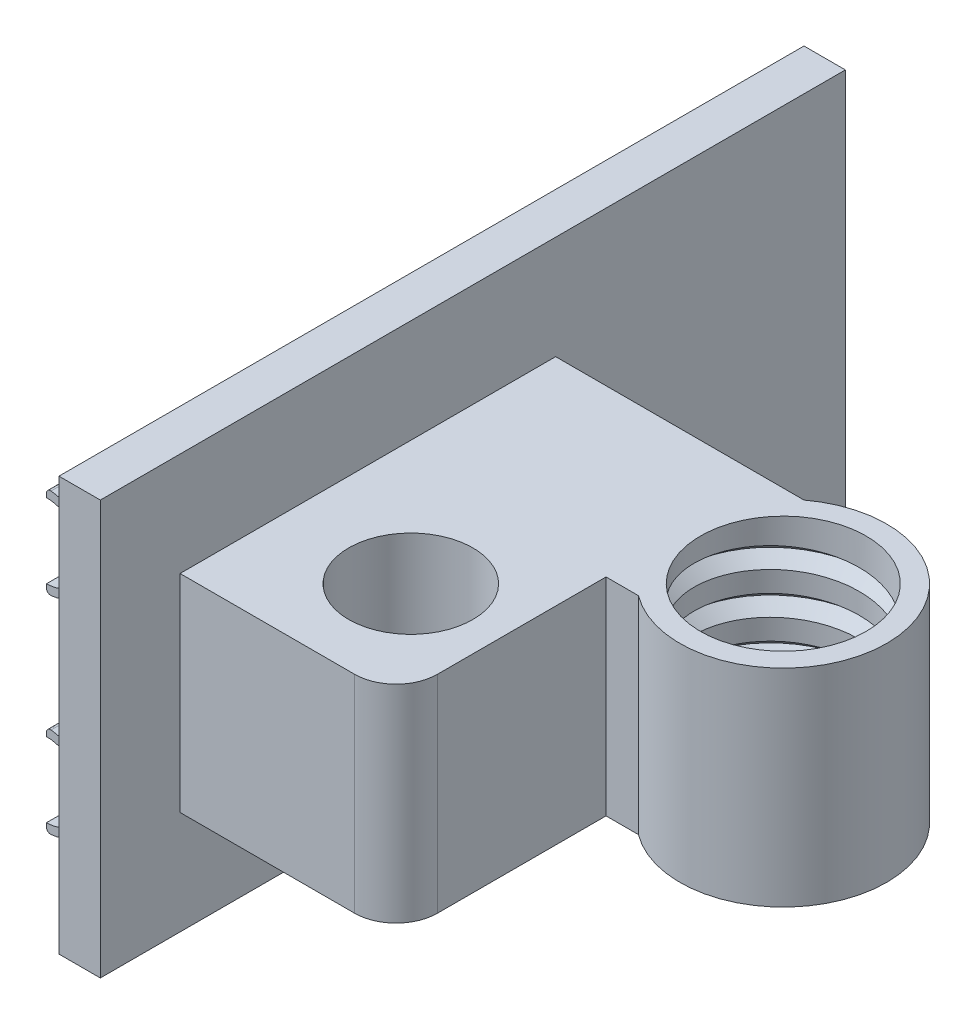
SolidWorks part; units mm, degrees
ref_plane "Front Plane" through (0, 0, 0) normal (0, 0, 1) x (1, 0, 0)
ref_plane "Top Plane" through (0, 0, 0) normal (0, 1, 0) x (1, 0, 0)
ref_plane "Right Plane" through (0, 0, 0) normal (1, 0, 0) x (0, 0, -1)
sketch "Sketch1" plane through (0, 0, 0) normal (0, 1, 0) x (1, 0, 0)
  line L0 (-75, 20) -> (-75, -20)
  line L1 (-15, 20) -> (-75, 20)
  line L3 (-75, -20) -> (-15, -20)
  circle A0 centre (0, 0) radius 20
  arc A1 (-15, -20) -> (-15, 20) centre (0, 0) ccw
  dimension "D1" = 40
  dimension "D2" = 50
  dimension "D3" = 60
extrude "Boss-Extrude1" add sketch "Sketch1" along normal blind 50
sketch "Sketch2" plane through (-75, 0, 0) normal (-1, 0, 0) x (0, 0, 1)
  line L0 (20, 50) -> (-20, 0)
  line L1 (-20, 50) -> (20, 0)
  line L3 (-90, -25) -> (90, -25)
  line L4 (-90, -25) -> (-90, 75)
  line L5 (-90, 75) -> (90, 75)
  line L6 (90, -25) -> (90, 75)
  line L7 (-90, -25) -> (90, 75) construction
  line L8 (-90, 75) -> (90, -25) construction
  point P8 (0, 25)
  dimension "D1" = 180
  dimension "D2" = 100
extrude "Boss-Extrude2" add sketch "Sketch2" along normal blind 10 contours L4 L5 L6 L3
sketch "Sketch11" plane through (0, 0, 0) normal (0, 0, 1) x (1, 0, 0)
  line L0 (-20, 50) -> (20, 50) construction
  line L1 (20, 50) -> (-20, 50) construction
  line L2 (25, 50) -> (-15, 50) construction
  line L3 (0, 50) -> (0, 0) construction
  line L4 (20, 50) -> (20, 45)
  line L5 (20, 45) -> (23.047, 47.5)
  line L6 (23.047, 47.5) -> (20, 50)
  dimension "D1" = 5
sketch "Sketch12" plane through (0, 50, 0) normal (0, 1, 0) x (1, 0, 0)
  circle A0 centre (0, 0) radius 20.1308
ref_plane "Plane2" through (0, 60, 0) normal (0, 1, 0) x (1, 0, 0)
sketch "Sketch13" plane through (0, 60, 0) normal (0, 1, 0) x (1, 0, 0)
  circle A0 centre (0, 0) radius 20 construction
  circle A1 centre (0, 0) radius 20
curve "Helix/Spiral2" pitch 10 height 72.5 turns 7.25
sweep "Cut-Sweep2" cut profiles "Sketch11" path "Helix/Spiral2"
sketch "Sketch14" plane through (0, 0, 90) normal (0, 0, 1) x (1, 0, 0)
  line L0 (-85, 25) -> (-85, 75) construction
  line L1 (-85, 25) -> (-116.7737, 25) construction
  line L2 (-85, 50) -> (-98, 50) construction
  line L3 (-85, 55.4817) -> (-88.4632, 55.4817)
  line L4 (-85, 44.5183) -> (-88.4632, 44.5183)
  line L5 (-98, 39) -> (-98, 41)
  line L6 (-98, 59) -> (-98, 61)
  line L7 (-85, 44.5183) -> (-85, 55.4817)
  line L8 (-85, 0) -> (-98, 0) construction
  line L9 (-85, 5.4817) -> (-85, -5.4817)
  line L10 (-98, -9) -> (-98, -11)
  line L11 (-98, 11) -> (-98, 9)
  line L12 (-85, 5.4817) -> (-88.4632, 5.4817)
  line L13 (-85, -5.4817) -> (-88.4632, -5.4817)
  arc A1 (-98, 39) -> (-88.4632, 44.5183) centre (-98, 50) ccw
  arc A2 (-90.862, 55.4817) -> (-98, 59) centre (-98, 50) ccw
  arc A3 (-90.862, 44.5183) -> (-98, 41) centre (-98, 50) cw
  arc A4 (-90.862, 44.5183) -> (-90.862, 55.4817) centre (-98, 50) ccw
  arc A5 (-88.4632, 55.4817) -> (-98, 61) centre (-98, 50) ccw
  arc A6 (-88.4632, -5.4817) -> (-98, -11) centre (-98, 0) cw
  arc A7 (-90.862, 5.4817) -> (-90.862, -5.4817) centre (-98, 0) cw
  arc A8 (-90.862, 5.4817) -> (-98, 9) centre (-98, 0) ccw
  arc A9 (-90.862, -5.4817) -> (-98, -9) centre (-98, 0) cw
  arc A10 (-98, 11) -> (-88.4632, 5.4817) centre (-98, 0) cw
  dimension "D2" = 13
extrude "Boss-Extrude3" add sketch "Sketch14" against normal blind 10 from offset 10 offset against normal yes
mirror "Mirror1" about plane through (0, 0, 0) normal (0, 0, 1) of "Boss-Extrude3"
sketch "Sketch15" plane through (0, 50, 0) normal (0, 1, 0) x (1, 0, 0)
  line L1 (-75, -20) -> (-27.8351, -20)
  line L2 (-75, -20) -> (-75, -70.7363)
  line L3 (-75, -70.7363) -> (-27.8351, -70.7363)
  line L4 (-27.8351, -20) -> (-27.8351, -70.7363)
extrude "Boss-Extrude4" add sketch "Sketch15" against normal up to surface (50 mm away) up to face at (-35, 0, 0)
sketch "Sketch16" plane through (0, 50, 0) normal (0, 1, 0) x (1, 0, 0)
  line L0 (-27.8351, -70.7363) -> (-27.8351, -20) construction
  line L1 (-75, -70.7363) -> (-27.8351, -70.7363) construction
  circle A0 centre (-44.9951, -44.9963) radius 15
  dimension "D1" = 30
  dimension "D2" = 17.16
  dimension "D3" = 25.74
extrude "Cut-Extrude1" cut sketch "Sketch16" against normal blind 67
sketch "Sketch18" plane through (0, 50, 0) normal (0, 1, 0) x (1, 0, 0)
  line L0 (-27.8351, -20) -> (-15, -20) construction
  line L1 (-27.8351, -70.7363) -> (-22.8246, -70.7363)
  line L2 (-27.8351, -70.7363) -> (-27.8351, -20)
  line L3 (-27.8351, -20) -> (-22.8246, -20)
  line L4 (-22.8246, -70.7363) -> (-22.8246, -20)
extrude "Boss-Extrude5" add sketch "Sketch18" against normal up to surface (50 mm away) up to face at (-44.9951, 0, 59.9963)
fillet "Fillet1" radius 10 1 edges at (-22.8246, 25, 70.7363)
fillet "Fillet2" radius 1 8 edges at (-98, 61, -75) (-98, 39, -75) (-98, 11, -75) (-98, -11, -75) (-98, -11, 75) (-98, 11, 75) (-98, 39, 75) (-98, 61, 75)
